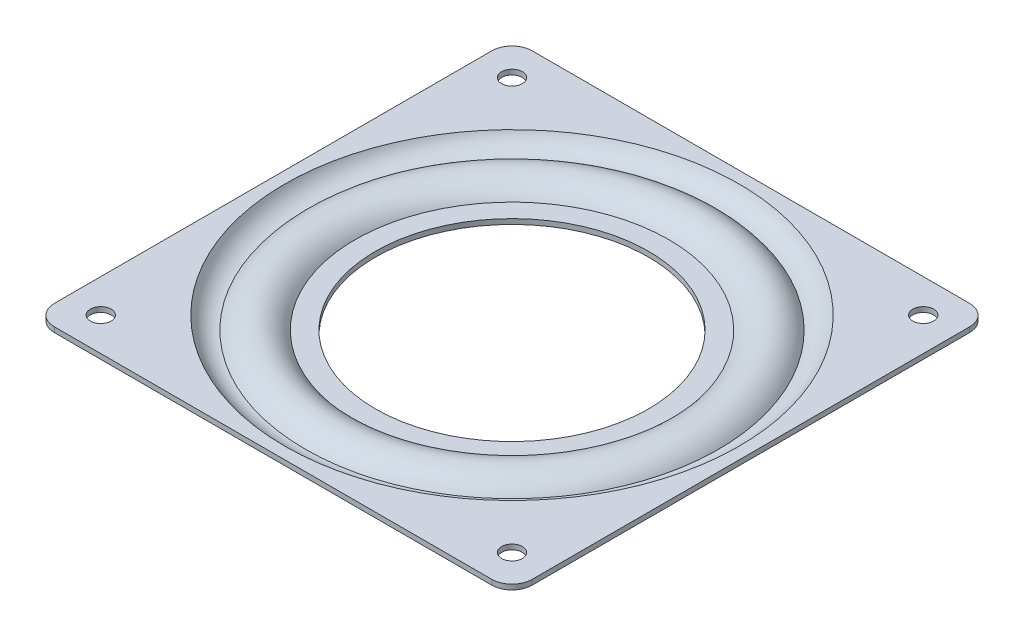
SolidWorks part; units mm, degrees
ref_plane "前视基准面" through (0, 0, 0) normal (0, 0, 1) x (1, 0, 0)
ref_plane "上视基准面" through (0, 0, 0) normal (0, 1, 0) x (1, 0, 0)
ref_plane "右视基准面" through (0, 0, 0) normal (1, 0, 0) x (0, 0, -1)
sketch "草图1" plane through (0, 0, 0) normal (0, 0, 1) x (1, 0, 0)
  line L0 (-36.7805, 0) -> (-35.9228, 0)
  line L1 (0, 6.9172) -> (0, -6.9172) construction
  line L2 (-31, -2.5698) -> (-27, -2.5698)
  line L3 (-35.9228, 0) -> (0, 0) construction
  line L4 (0, 0) -> (43.3864, 0) construction
  line L5 (-43.3864, 0) -> (-36.7805, 0) construction
  line L6 (-31.5531, -3.5698) -> (-27, -3.5698)
  line L7 (-27, -2.5698) -> (-27, -3.5698)
  line L8 (-44.9105, 0) -> (-45.8139, -0.4289)
  arc A0 (-44.9105, 0) -> (-40.8455, -2.5698) centre (-40.8455, 1.9302) ccw
  arc A1 (-40.8455, -2.5698) -> (-31, -2.5698) centre (-35.9228, -6) cw
  arc A2 (-40.8455, -2.5698) -> (-36.8127, -0.0664) centre (-40.8455, 1.9302) ccw construction
  arc A3 (-36.8127, -0.0664) -> (-36.7805, 0) centre (-40.8455, 1.9302) ccw
  arc A4 (-45.8139, -0.4289) -> (-40.2759, -3.5402) centre (-40.8455, 1.9302) ccw
  arc A5 (-40.2759, -3.5402) -> (-31.5531, -3.5698) centre (-35.9228, -6) cw
  point P4 (0, 0)
  point P8 (0, 0)
  dimension "D1" = 4.5
  dimension "D2" = 6
  dimension "D3" = 27
  dimension "D4" = 4
revolve "旋转1" add sketch "草图1" angle 360 about L1 region at (-33.2348, -0.8509, 0)
sketch "草图2" plane through (0, 0, 0) normal (0, 1, 0) x (1, 0, 0)
  line L0 (0, 0) -> (-40.6586, 40.6586) construction
  line L1 (-43.25, 47.25) -> (47.25, 47.25)
  line L2 (-47.25, 43.25) -> (-47.25, -47.25)
  line L3 (-47.25, -47.25) -> (47.25, -47.25)
  line L4 (47.25, 47.25) -> (47.25, -47.25)
  line L5 (-47.25, 47.25) -> (47.25, -47.25) construction
  line L6 (-47.25, -47.25) -> (47.25, 47.25) construction
  line L7 (0, 0) -> (40.6586, 40.6586) construction
  line L8 (0, 0) -> (-43.25, 43.25) construction
  circle A0 centre (0, 0) radius 44.9105 construction
  circle A1 centre (0, 0) radius 44.9105
  arc A2 (-43.25, 47.25) -> (-47.25, 43.25) centre (-43.25, 43.25) ccw
  circle A3 centre (-40.6586, 40.6586) radius 2.05
  circle A4 centre (40.6586, 40.6586) radius 2.05
  circle A5 centre (40.6586, -40.6586) radius 2.05
  circle A6 centre (-40.6586, -40.6586) radius 2.05
  arc A7 (47.25, 43.25) -> (43.25, 47.25) centre (43.25, 43.25) ccw
  arc A8 (43.25, -47.25) -> (47.25, -43.25) centre (43.25, -43.25) ccw
  arc A9 (-47.25, -43.25) -> (-43.25, -47.25) centre (-43.25, -43.25) ccw
  dimension "D3" = 4
  dimension "D4" = 4.1
  dimension "D9" = 4
  dimension "D1" = 94.5
  dimension "D2" = 94.5
  dimension "D5" = 57.5
  dimension "D7" = 90
  dimension "D8" = 57.5
  dimension "D10" = 61.1647
  dimension "D6" = 4
extrude "凸台-拉伸1" add sketch "草图2" against normal blind 1 contours L2 A9 L3 A8 L4 A7 L1 A2 A6 A5 A4 A3 A1 region at (0, 0, -45.9136)
sketch "Sketch2" plane through (0, -1, 0) normal (0, -1, 0) x (1, 0, 0)
  line L0 (-40.6586, 40.6586) -> (-40.6586, 38.6086) construction
  circle A0 centre (-40.6586, 40.6586) radius 2.05 construction
